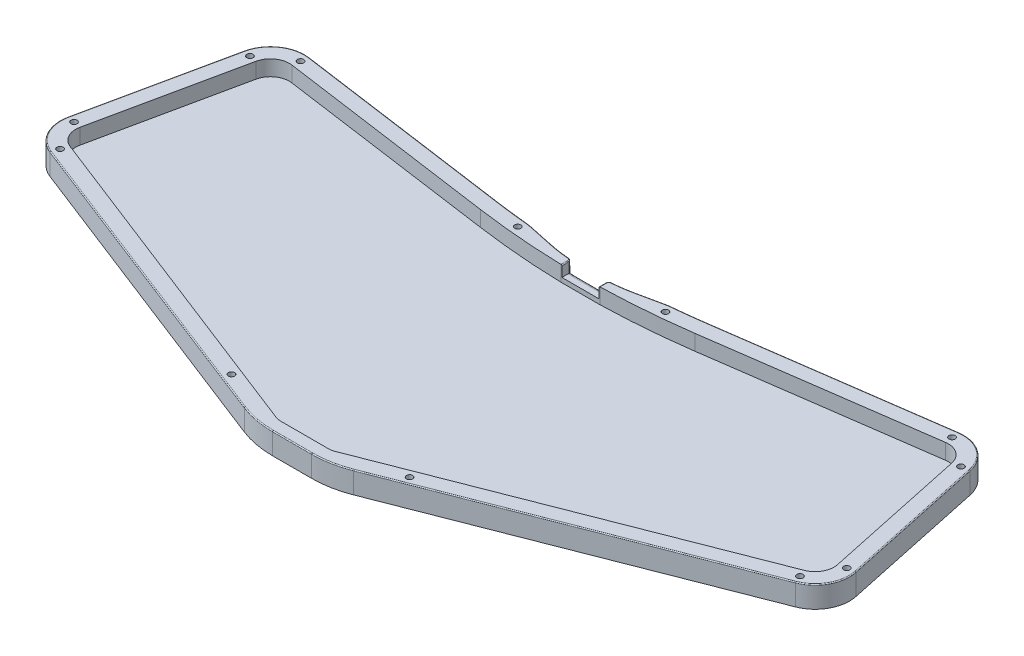
SolidWorks part; units mm, degrees
ref_plane "Front Plane" through (0, 0, 0) normal (0, 0, 1) x (1, 0, 0)
ref_plane "Top Plane" through (0, 0, 0) normal (0, 1, 0) x (1, 0, 0)
ref_plane "Right Plane" through (0, 0, 0) normal (1, 0, 0) x (0, 0, -1)
sketch "Sketch1" plane through (0, 0, 0) normal (0, 1, 0) x (1, 0, 0)
  line L0 (79.8359, 54.9433) -> (9.0142, 64.8966)
  line L1 (2.1986, 60.1242) -> (-7.7511, 13.3146)
  line L2 (-3.9994, 6.3627) -> (98.6981, -33.6603)
  line L3 (114.4761, -36.4417) -> (109.4761, -36.4417)
  line L4 (114.4761, -36.4417) -> (119.4761, -36.4417)
  line L5 (98.6981, -33.6603) -> (104.9596, -36.1005)
  line L6 (130.2541, -33.6603) -> (123.9926, -36.1005)
  line L7 (109.4761, -36.4417) -> (107.9761, -36.4417)
  line L8 (119.4761, -36.4417) -> (120.9761, -36.4417)
  line L9 (107.9761, -36.4417) -> (106.7752, -36.4417)
  line L10 (120.9761, -36.4417) -> (122.177, -36.4417)
  line L11 (130.2541, -33.6603) -> (232.9516, 6.3627)
  line L12 (236.7033, 13.3146) -> (226.7536, 60.1242)
  line L13 (219.9379, 64.8966) -> (149.1163, 54.9433)
  line L14 (3.6714, 60.5601) -> (-6.861, 11.0092)
  line L15 (-6.861, 11.0092) -> (-6.9321, 10.6746)
  line L16 (-6.3544, 9.785) -> (1.0894, 8.2028)
  line L17 (1.0894, 8.2028) -> (9.785, 6.3544)
  line L18 (27.0739, 4.7243) -> (11.2279, 8.0924)
  line L19 (10.6745, 6.9321) -> (10.872, 7.8614)
  line L20 (28.2649, 6.7203) -> (27.9634, 5.3019)
  line L21 (28.6207, 6.9513) -> (44.1732, 3.6455)
  line L22 (41.5559, -10.1109) -> (44.4043, 3.2897)
  line L23 (42.1336, -11.0005) -> (57.9796, -14.3686)
  line L24 (57.9092, -16.1428) -> (58.2107, -14.7244)
  line L25 (74.4684, -20.4293) -> (58.4869, -17.0323)
  line L26 (77.5795, -21.4389) -> (100.2893, -33.0102)
  line L27 (101.2978, -32.6822) -> (108.7886, -17.9806)
  line L28 (108.4608, -16.9719) -> (98.6245, -11.96)
  line L29 (96.3912, -4.6423) -> (98.4012, 4.8138)
  line L30 (98.4012, 4.8138) -> (106.9948, 45.2436)
  line L31 (106.417, 46.1328) -> (90.2776, 49.5633)
  line L32 (89.388, 48.9856) -> (89.1905, 48.0564)
  line L33 (88.8347, 47.8253) -> (73.2821, 51.1311)
  line L34 (73.3526, 52.9053) -> (73.0511, 51.4869)
  line L35 (72.7749, 53.7948) -> (56.6354, 57.2253)
  line L36 (55.7459, 56.6477) -> (55.4444, 55.2294)
  line L37 (21.8498, 59.5076) -> (37.6958, 56.1394)
  line L38 (20.9602, 58.9299) -> (20.7627, 58.0006)
  line L39 (4.5609, 61.1377) -> (20.4069, 57.7696)
  line L40 (39.2426, 58.3664) -> (55.0886, 54.9983)
  line L41 (38.0516, 56.3705) -> (38.3531, 57.7888)
  line L42 (225.2808, 60.5601) -> (235.8132, 11.0092)
  line L43 (235.8132, 11.0092) -> (235.8843, 10.6746)
  line L44 (235.3066, 9.785) -> (227.8628, 8.2028)
  line L45 (227.8628, 8.2028) -> (219.1672, 6.3544)
  line L46 (201.8783, 4.7243) -> (217.7243, 8.0924)
  line L47 (218.2776, 6.9321) -> (218.0801, 7.8614)
  line L48 (200.6873, 6.7203) -> (200.9888, 5.3019)
  line L49 (200.3315, 6.9513) -> (184.7789, 3.6455)
  line L50 (187.3963, -10.1109) -> (184.5479, 3.2897)
  line L51 (186.8186, -11.0005) -> (170.9726, -14.3686)
  line L52 (171.043, -16.1428) -> (170.7415, -14.7244)
  line L53 (154.4838, -20.4293) -> (170.4653, -17.0323)
  line L54 (151.3727, -21.4389) -> (128.6628, -33.0102)
  line L55 (127.6544, -32.6822) -> (120.1636, -17.9806)
  line L56 (120.4913, -16.9719) -> (130.3277, -11.96)
  line L57 (132.561, -4.6423) -> (130.551, 4.8138)
  line L58 (130.551, 4.8138) -> (121.9576, 45.2428)
  line L59 (122.5352, 46.1328) -> (138.6746, 49.5633)
  line L60 (139.5641, 48.9856) -> (139.7617, 48.0564)
  line L61 (140.1175, 47.8253) -> (155.67, 51.1311)
  line L62 (155.5996, 52.9053) -> (155.9011, 51.4869)
  line L63 (156.1773, 53.7948) -> (172.3167, 57.2253)
  line L64 (173.2063, 56.6477) -> (173.5078, 55.2294)
  line L65 (207.1024, 59.5076) -> (191.2564, 56.1394)
  line L66 (207.9919, 58.9299) -> (208.1894, 58.0006)
  line L67 (224.3913, 61.1377) -> (208.5453, 57.7696)
  line L68 (189.7096, 58.3664) -> (173.8636, 54.9983)
  line L69 (190.9006, 56.3705) -> (190.5991, 57.7888)
  line L70 (79.7802, 54.5472) -> (8.9586, 64.5005)
  line L71 (2.5898, 60.0411) -> (-7.3599, 13.2314)
  line L72 (-3.8542, 6.7354) -> (98.8433, -33.2876)
  line L73 (98.8433, -33.2876) -> (105.1048, -35.7278)
  line L74 (107.9761, -36.0417) -> (106.7752, -36.0417)
  line L75 (109.4761, -36.0417) -> (107.9761, -36.0417)
  line L76 (114.4761, -36.0417) -> (109.4761, -36.0417)
  line L77 (114.4761, -36.0417) -> (119.4761, -36.0417)
  line L78 (119.4761, -36.0417) -> (120.9761, -36.0417)
  line L79 (120.9761, -36.0417) -> (122.177, -36.0417)
  line L80 (130.1088, -33.2876) -> (123.8474, -35.7278)
  line L81 (130.1088, -33.2876) -> (232.8064, 6.7354)
  line L82 (236.312, 13.2314) -> (226.3623, 60.0411)
  line L83 (219.9936, 64.5005) -> (149.1719, 54.5472)
  line L84 (74.4684, -20.4293) -> (75.1187, -20.5675)
  line L85 (96.3912, -4.6423) -> (96.0037, -6.4654)
  line L86 (132.561, -4.6423) -> (132.9485, -6.4654)
  line L87 (154.4838, -20.4293) -> (153.8335, -20.5675)
  line L88 (111.3394, 55.5642) -> (117.6128, 55.5642)
  line L89 (108.1261, 52.602) -> (120.8261, 52.602)
  line L90 (108.1159, 52.2022) -> (120.8363, 52.2022)
  line L91 (80.5318, 59.8946) -> (9.7101, 69.848)
  line L92 (-2.6922, 61.1638) -> (-12.6419, 14.3541)
  line L93 (-5.815, 1.7039) -> (96.8825, -38.319)
  line L94 (108.1754, -40.4417) -> (114.4761, -40.4417)
  line L95 (114.4761, -40.4417) -> (120.7768, -40.4417)
  line L96 (132.0697, -38.319) -> (234.7672, 1.7039)
  line L97 (241.594, 14.3541) -> (231.6443, 61.1638)
  line L98 (219.2421, 69.848) -> (148.4204, 59.8946)
  line L99 (100.9438, 56.6568) -> (93.1162, 58.3206)
  line L100 (128.0084, 56.6568) -> (135.8359, 58.3206)
  arc A0 (79.8359, 54.9433) -> (108.1261, 52.602) centre (114.4761, 301.421) ccw
  arc A1 (9.0142, 64.8966) -> (2.1986, 60.1242) centre (8.1653, 58.856) ccw
  arc A2 (-7.7511, 13.3146) -> (-3.9994, 6.3627) centre (-1.7844, 12.0463) ccw
  arc A3 (232.9516, 6.3627) -> (236.7033, 13.3146) centre (230.7366, 12.0463) ccw
  arc A4 (226.7536, 60.1242) -> (219.9379, 64.8966) centre (220.7869, 58.856) ccw
  arc A5 (120.8261, 52.602) -> (149.1163, 54.9433) centre (114.4761, 301.421) ccw
  arc A6 (104.9596, -36.1005) -> (106.7752, -36.4417) centre (106.7752, -31.4417) ccw
  arc A7 (122.177, -36.4417) -> (123.9926, -36.1005) centre (122.177, -31.4417) ccw
  arc A8 (-6.9321, 10.6746) -> (-6.3544, 9.785) centre (-6.1985, 10.5186) ccw
  arc A9 (9.785, 6.3544) -> (10.6745, 6.9321) centre (9.9409, 7.0881) ccw
  arc A10 (27.0739, 4.7243) -> (27.9634, 5.3019) centre (27.2298, 5.4579) ccw
  arc A11 (11.2279, 8.0924) -> (10.872, 7.8614) centre (11.1655, 7.799) ccw
  arc A12 (41.5559, -10.1109) -> (42.1336, -11.0005) centre (42.2895, -10.2668) ccw
  arc A13 (57.9092, -16.1428) -> (58.4869, -17.0323) centre (58.6428, -16.2987) ccw
  arc A14 (28.6207, 6.9513) -> (28.2649, 6.7203) centre (28.5583, 6.6579) ccw
  arc A15 (44.4043, 3.2897) -> (44.1732, 3.6455) centre (44.1109, 3.3521) ccw
  arc A16 (58.2107, -14.7244) -> (57.9796, -14.3686) centre (57.9172, -14.6621) ccw
  arc A17 (100.2893, -33.0102) -> (101.2978, -32.6822) centre (100.6295, -32.3417) ccw
  arc A18 (108.7886, -17.9806) -> (108.4608, -16.9719) centre (108.1204, -17.6401) ccw
  arc A19 (106.9948, 45.2436) -> (106.417, 46.1328) centre (106.2611, 45.3992) ccw
  arc A20 (90.2776, 49.5633) -> (89.388, 48.9856) centre (90.1216, 48.8297) ccw
  arc A21 (73.3526, 52.9053) -> (72.7749, 53.7948) centre (72.6189, 53.0612) ccw
  arc A22 (56.6354, 57.2253) -> (55.7459, 56.6477) centre (56.4795, 56.4917) ccw
  arc A23 (21.8498, 59.5076) -> (20.9602, 58.9299) centre (21.6939, 58.7739) ccw
  arc A24 (4.5609, 61.1377) -> (3.6714, 60.5601) centre (4.405, 60.4041) ccw
  arc A25 (88.8347, 47.8253) -> (89.1905, 48.0564) centre (88.8971, 48.1188) ccw
  arc A26 (73.0511, 51.4869) -> (73.2821, 51.1311) centre (73.3445, 51.4246) ccw
  arc A27 (20.4069, 57.7696) -> (20.7627, 58.0006) centre (20.4693, 58.063) ccw
  arc A28 (37.6958, 56.1394) -> (38.0516, 56.3705) centre (37.7582, 56.4328) ccw
  arc A29 (55.0886, 54.9983) -> (55.4444, 55.2294) centre (55.151, 55.2917) ccw
  arc A30 (39.2426, 58.3664) -> (38.3531, 57.7888) centre (39.0867, 57.6328) ccw
  arc A31 (235.3066, 9.785) -> (235.8843, 10.6746) centre (235.1507, 10.5186) ccw
  arc A32 (218.2776, 6.9321) -> (219.1672, 6.3544) centre (219.0113, 7.0881) ccw
  arc A33 (200.9888, 5.3019) -> (201.8783, 4.7243) centre (201.7224, 5.4579) ccw
  arc A34 (218.0801, 7.8614) -> (217.7243, 8.0924) centre (217.7867, 7.799) ccw
  arc A35 (186.8186, -11.0005) -> (187.3963, -10.1109) centre (186.6626, -10.2668) ccw
  arc A36 (170.4653, -17.0323) -> (171.043, -16.1428) centre (170.3094, -16.2987) ccw
  arc A37 (200.6873, 6.7203) -> (200.3315, 6.9513) centre (200.3939, 6.6579) ccw
  arc A38 (184.7789, 3.6455) -> (184.5479, 3.2897) centre (184.8413, 3.3521) ccw
  arc A39 (170.9726, -14.3686) -> (170.7415, -14.7244) centre (171.035, -14.6621) ccw
  arc A40 (127.6544, -32.6822) -> (128.6635, -33.0098) centre (128.3227, -32.3417) ccw
  arc A41 (120.4913, -16.9719) -> (120.1636, -17.9806) centre (120.8318, -17.6401) ccw
  arc A42 (122.5352, 46.1328) -> (121.9576, 45.2428) centre (122.6911, 45.3992) ccw
  arc A43 (139.5641, 48.9856) -> (138.6746, 49.5633) centre (138.8305, 48.8297) ccw
  arc A44 (156.1773, 53.7948) -> (155.5996, 52.9053) centre (156.3332, 53.0612) ccw
  arc A45 (173.2063, 56.6477) -> (172.3167, 57.2253) centre (172.4727, 56.4917) ccw
  arc A46 (207.9919, 58.9299) -> (207.1024, 59.5076) centre (207.2583, 58.7739) ccw
  arc A47 (225.2808, 60.5601) -> (224.3913, 61.1377) centre (224.5472, 60.4041) ccw
  arc A48 (139.7617, 48.0564) -> (140.1175, 47.8253) centre (140.0551, 48.1188) ccw
  arc A49 (155.67, 51.1311) -> (155.9011, 51.4869) centre (155.6077, 51.4246) ccw
  arc A50 (208.1894, 58.0006) -> (208.5453, 57.7696) centre (208.4829, 58.063) ccw
  arc A51 (190.9006, 56.3705) -> (191.2564, 56.1394) centre (191.194, 56.4328) ccw
  arc A52 (173.5078, 55.2294) -> (173.8636, 54.9983) centre (173.8012, 55.2917) ccw
  arc A53 (190.5991, 57.7888) -> (189.7096, 58.3664) centre (189.8655, 57.6328) ccw
  circle A54 centre (13.0465, 61.3788) radius 1
  circle A55 centre (18.3804, 3.5051) radius 1
  circle A56 centre (81.4742, 51.4345) radius 1
  circle A57 centre (114.4761, -18.3417) radius 1
  circle A58 centre (114.4761, 38.421) radius 1
  circle A59 centre (147.4779, 51.4345) radius 1
  circle A60 centre (215.9057, 61.3788) radius 1
  circle A61 centre (210.5718, 3.5051) radius 1
  arc A62 (79.7802, 54.5472) -> (108.1159, 52.2022) centre (114.4761, 301.421) ccw
  arc A63 (8.9586, 64.5005) -> (2.5898, 60.0411) centre (8.1653, 58.856) ccw
  arc A64 (-7.3599, 13.2314) -> (-3.8542, 6.7354) centre (-1.7844, 12.0463) ccw
  arc A65 (105.1048, -35.7278) -> (106.7752, -36.0417) centre (106.7752, -31.4417) ccw
  arc A66 (122.177, -36.0417) -> (123.8474, -35.7278) centre (122.177, -31.4417) ccw
  arc A67 (232.8064, 6.7354) -> (236.312, 13.2314) centre (230.7366, 12.0463) ccw
  arc A68 (226.3623, 60.0411) -> (219.9936, 64.5005) centre (220.7869, 58.856) ccw
  arc A69 (120.8363, 52.2022) -> (149.1719, 54.5472) centre (114.4761, 301.421) ccw
  arc A70 (77.5795, -21.4389) -> (75.1187, -20.5675) centre (73.0396, -30.349) ccw
  arc A71 (96.0037, -6.4654) -> (98.6245, -11.96) centre (100.8944, -7.505) ccw
  arc A72 (153.8335, -20.5675) -> (151.3727, -21.4389) centre (155.9126, -30.349) ccw
  arc A73 (130.3277, -11.96) -> (132.9485, -6.4654) centre (128.0578, -7.505) ccw
  arc A74 (80.5318, 59.8946) -> (90.8919, 58.6639) centre (114.4761, 301.421) ccw
  arc A75 (9.7101, 69.848) -> (-2.6922, 61.1638) centre (8.1653, 58.856) ccw
  arc A76 (-12.6419, 14.3541) -> (-5.815, 1.7039) centre (-1.7844, 12.0463) ccw
  arc A77 (96.8825, -38.319) -> (108.1754, -40.4417) centre (108.1754, -9.3417) ccw
  arc A78 (120.7768, -40.4417) -> (132.0697, -38.319) centre (120.7768, -9.3417) ccw
  arc A79 (234.7672, 1.7039) -> (241.594, 14.3541) centre (230.7366, 12.0463) ccw
  arc A80 (231.6443, 61.1638) -> (219.2421, 69.848) centre (220.7869, 58.856) ccw
  arc A81 (138.0602, 58.6639) -> (148.4204, 59.8946) centre (114.4761, 301.421) ccw
  arc A82 (93.1162, 58.3206) -> (90.8919, 58.6639) centre (88.958, 38.7577) ccw
  arc A83 (138.0602, 58.6639) -> (135.8359, 58.3206) centre (139.9942, 38.7577) ccw
  arc A84 (100.9438, 56.6568) -> (111.3394, 55.5642) centre (111.3394, 105.5642) ccw
  arc A85 (117.6128, 55.5642) -> (128.0084, 56.6568) centre (117.6128, 105.5642) ccw
  circle A86 centre (-10.1965, 13.8343) radius 1
  circle A87 centre (239.1487, 13.8343) radius 1
  circle A88 centre (-0.2468, 60.644) radius 1
  circle A89 centre (229.199, 60.644) radius 1
  circle A90 centre (143.2179, -31.2912) radius 1
  circle A91 centre (85.7343, -31.2912) radius 1
  circle A92 centre (9.3622, 67.3723) radius 1
  circle A93 centre (90.6502, 56.1756) radius 1
  circle A94 centre (138.302, 56.1756) radius 1
  circle A95 centre (219.59, 67.3723) radius 1
  circle A96 centre (-4.9072, 4.0333) radius 1
  circle A97 centre (233.8594, 4.0333) radius 1
extrude "Boss-Extrude1" add sketch "Sketch1" along normal blind 7 contours A85 L88 A84 L99 A82 A74 L91 A75 L92 A76 L93 A77 L94 L95 A78 L96 A79 L97 A80 L98 A81 A83 L100 A97 A96 A95 A94 A93 A92 A91 A90 A89 A88 A87 A86 A7 L10 L8 region at (114.4761, 0, -52.788)
extrude "Boss-Extrude2" add sketch "Sketch1<3>" along normal blind 2 contours A69 L90 A62 L70 A63 L71 A64 L72 L73 A65 L74 L75 L76 L77 L78 L79 A66 L80 L81 A67 L82 A68 L83 A61 A60 A59 A58 A57 A56 A55 A54 L85 A71 L28 A18 L27 A17 L26 A70 L84 L25 A13 | L10 A7 L6 L11 A3 L12 A4 L13 A5 L89 A0 L0 A1 L1 A2 L2 L5 A6 L9 L7 L3 L4 L8 L90 A69 L83 A68 L82 A67 L81 L80 A66 L79 L78 L77 L76 L75 L74 A65 L73 L72 A64 L71 A63 L70 A62 | A57 | A58 | A59 | A56 | A54 | A55 | A61 | A60 | A73 L56 A41 L55 A40 L54 A72 L87 L53 A36 L52 A39 L51 A35 L50 A38 L49 A37 L48 A33 L46 A34 L47 A32 L45 L44 A31 L43 L42 A47 L67 A50 L66 A46 L65 A51 L69 A53 L68 A52 L64 A45 L63 A44 L62 A49 L61 A48 L60 A43 | A71 L85 L29 L30 A19 L31 A20 L32 A25 L33 A26 L34 A21 L35 A22 L36 A29 L40 A30 L41 A28 L37 A23 L38 A27 L39 A24 L14 L15 A8 L16 L17 A9 L19 A11 L18 A10 L20 A14 L21 A15 L22 A12 L23 A16 L24 A13 L25 L84 A70 L26 | A96 | A86 | A88 | A92 | A93 | A94 | A95 | A89 | A97 | A87 | A90 | A91 region at (93.9257, 0, -53.105) region at (54.8314, 0, -21.3337) region at (174.1207, 0, -21.3337) region at (114.4761, 0, -12.873) region at (13.0465, 0, -61.3788) region at (18.3804, 0, -3.5051) region at (81.4742, 0, -51.4345) region at (114.4761, 0, 18.3417) region at (114.4761, 0, -38.421) region at (147.4779, 0, -51.4345) region at (215.9057, 0, -61.3788) region at (210.5718, 0, -3.5051) region at (-10.1965, 0, -13.8343) region at (239.1487, 0, -13.8343) region at (-0.2468, 0, -60.644) region at (229.199, 0, -60.644) region at (143.2179, 0, 31.2912) region at (85.7343, 0, 31.2912) region at (9.3622, 0, -67.3723) region at (90.6502, 0, -56.1756) region at (138.302, 0, -56.1756) region at (219.59, 0, -67.3723) region at (-4.9072, 0, -4.0333) region at (233.8594, 0, -4.0333)
sketch "Sketch1<3>" plane through (0, 0, 0) normal (0, 1, 0) x (1, 0, 0) same geometry as "Sketch1"
sketch "Sketch2" plane through (0, 0, -55.5642) normal (0, 0, -1) x (-1, 0, 0)
  line L0 (-114.4761, 7) -> (-114.4761, 3.5) construction
  line L1 (-111.3394, 7) -> (-117.6128, 7) construction
  line L2 (-114.4761, 7) -> (-120.4761, 7)
  line L3 (-120.4761, 7) -> (-120.4761, 3.5)
  line L4 (-120.4761, 3.5) -> (-114.4761, 3.5)
  line L5 (-114.4761, 3.5) -> (-108.4761, 3.5)
  line L6 (-108.4761, 3.5) -> (-108.4761, 7)
  line L7 (-108.4761, 7) -> (-114.4761, 7)
extrude "Cut-Extrude1" cut sketch "Sketch2" against normal blind 9
extrude "Cut-Extrude2" cut sketch "Sketch2<2>" along normal blind 9
sketch "Sketch2<2>" plane through (0, 0, -55.5642) normal (0, 0, -1) x (-1, 0, 0) same geometry as "Sketch2"
fillet "Fillet1" radius 1 5 edges at (109.9071, 3.5, -55.5847) (114.4761, 3.5, -55.5642) (108.4761, 5.25, -55.6462) (119.045, 3.5, -55.5847) (120.4761, 5.25, -55.6462)
fillet "Fillet2" radius 0.3 25 edges at (108.4761, 7, -53.6564) (120.4761, 7, -53.6564) (108.2095, 7, -55.3905) (120.7427, 7, -55.3905) (104.232, 7, -56.0719) (124.7202, 7, -56.0719) (97.03, 7, -57.4887) (131.9222, 7, -57.4887) (92.0089, 7, -58.5236) (136.9433, 7, -58.5236) (85.7053, 7, -59.2239) (143.2469, 7, -59.2239) (45.1209, 7, -64.8713) (183.8312, 7, -64.8713) (1.7986, 7, -67.9486) (227.1536, 7, -67.9486) (-7.667, 7, -37.759) (236.6192, 7, -37.759) (-11.5527, 7, -6.7747) (240.5049, 7, -6.7747) (45.5337, 7, 18.3075) (183.4184, 7, 18.3075) (102.4301, 7, 39.9064) (126.5221, 7, 39.9064) (114.4761, 7, 40.4417)
